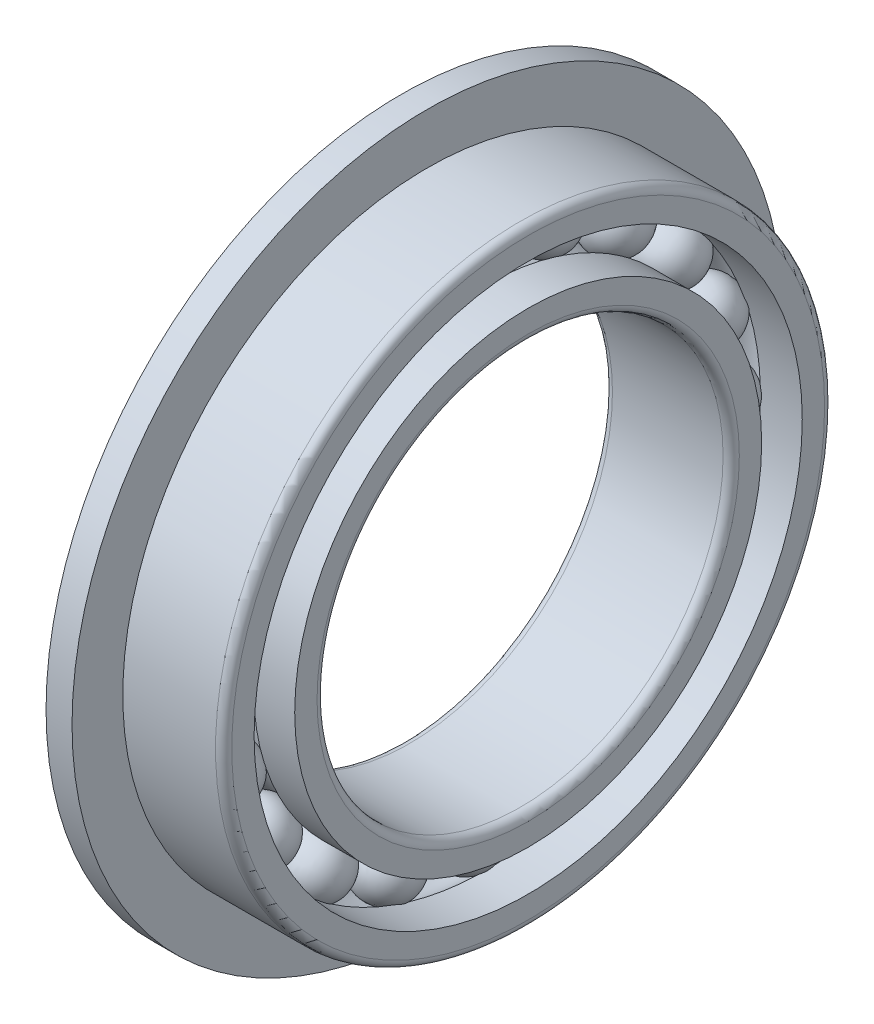
SolidWorks part; units mm, degrees
material "AISI 316 Stainless Steel Sheet (SS)"
ref_plane "Plane1" through (0, 0, 0) normal (0, 0, 1) x (1, 0, 0)
ref_plane "Plane2" through (0, 0, 0) normal (0, 1, 0) x (1, 0, 0)
ref_plane "Plane3" through (0, 0, 0) normal (1, 0, 0) x (0, 0, -1)
sketch "Clipboard" plane through (0, 0, 0) normal (0, 0, 1) x (1, 0, 0)
  line L0 (-10, 0) -> (10, 0) construction
  line L1 (0, 0) -> (21.0122, -7.6478)
  line L2 (0, 0) -> (7.4588, 2.7148)
  line L3 (0, 0) -> (21.0122, -7.6478)
  line L4 (0, 0) -> (-22.3573, -0.3902)
  dimension "BallCLRad" = 7.9375
sketch "CagSpiSke" plane through (0, 0, 0) normal (0, 0, 1) x (1, 0, 0)
  line L0 (0.0952, 7.7787) -> (0.0953, 8.0962)
  line L1 (0.0953, 8.0962) -> (-0.0953, 8.0962)
  line L2 (-0.0953, 8.0962) -> (-0.0952, 7.7787)
  line L3 (-0.0952, 7.7787) -> (0.0952, 7.7787)
  line L4 (-20.6375, 0) -> (20.6375, 0) construction
  line L5 (0, 0) -> (0, 23.7692) construction
  dimension "OD" = 16.1925
  dimension "ID" = 15.5575
revolve "CageSpine" add sketch "CagSpiSke" angle 0.001 about L4 reverse direction yes
ref_axis "Axis1" through (-50, 0, 0) along (1, 0, 0)
sketch "CagBalSke" plane through (0, 0, 0) normal (0, 0, 1) x (1, 0, 0)
  line L0 (-1.0478, 7.9375) -> (1.0478, 7.9375)
  line L1 (-1.905, 7.9375) -> (1.905, 7.9375) construction
  line L2 (-10, 0) -> (10, 0) construction
  line L3 (0, 0) -> (0, 24) construction
  arc A0 (1.0478, 7.9375) -> (-1.0478, 7.9375) centre (0, 7.9375) cw
  dimension "BallCLRad" = 7.9375
revolve "CageBall" [suppressed] add sketch "CagBalSke" angle 360 about L1 reverse direction yes
pattern_circular "CageBalls" [suppressed] count 20 every 18 about axis through (-50, 0, 0) along (1, 0, 0)
sketch "CagTrmODSke" plane through (0, 0, 0) normal (0, 0, 1) x (1, 0, 0)
  line L0 (1.0732, 8.0962) -> (1.0732, 9.0107)
  line L1 (1.0732, 9.0107) -> (-1.0732, 9.0107)
  line L2 (-1.0732, 9.0107) -> (-1.0732, 8.0962)
  line L3 (-1.0732, 8.0962) -> (1.0732, 8.0962)
  line L4 (-20.6375, 0) -> (20.6375, 0) construction
  line L5 (0, 0) -> (0, 25) construction
  dimension "Width" = 2.1463
  dimension "ID" = 16.1925
  dimension "OD" = 18.0213
revolve "CageTrimOD" [suppressed] cut sketch "CagTrmODSke" angle 360 about L4 reverse direction yes
sketch "CagTrmIDSke" plane through (0, 0, 0) normal (0, 0, 1) x (1, 0, 0)
  line L0 (1.0732, 6.9151) -> (1.0732, 7.7787)
  line L1 (1.0732, 7.7787) -> (-1.0732, 7.7787)
  line L2 (-1.0732, 7.7787) -> (-1.0732, 6.9151)
  line L3 (-1.0732, 6.9151) -> (1.0732, 6.9151)
  line L4 (-20.6375, 0) -> (20.6375, 0) construction
  line L5 (0, 0) -> (0, 25) construction
  dimension "Width" = 2.1463
  dimension "ID" = 13.8303
  dimension "OD" = 15.5575
revolve "CageTrimID" [suppressed] cut sketch "CagTrmIDSke" angle 360 about L4 reverse direction yes
sketch "BalSimSke" plane through (0, 0, 0) normal (0, 0, 1) x (1, 0, 0)
  line L0 (-10, 0) -> (10, 0) construction
  line L1 (-10, 7.9375) -> (10, 7.9375) construction
  line L2 (0, 0) -> (0, 23) construction
  circle A0 centre (0, 7.9375) radius 0.9525
  dimension "BallCLRad" = 7.9375
  dimension "Ball_diameter" = 1.905
revolve "BallsSimplified" [suppressed] add sketch "BalSimSke" angle 360 about L0
sketch "BalDetSke" plane through (0, 0, 0) normal (0, 0, 1) x (1, 0, 0)
  line L0 (-0.9525, 7.9375) -> (0.9525, 7.9375)
  line L1 (-1.905, 7.9375) -> (1.905, 7.9375) construction
  line L2 (0, 0) -> (0, 25) construction
  arc A0 (0.9525, 7.9375) -> (-0.9525, 7.9375) centre (0, 7.9375) cw
  dimension "BallCLRad" = 7.9375
  dimension "Ball_diameter" = 1.905
revolve "BallDetailed" add sketch "BalDetSke" angle 360 about L1 reverse direction yes
sketch "InnRacSke" plane through (0, 0, 0) normal (0, 0, 1) x (1, 0, 0)
  line L0 (-0.6501, 7.3025) -> (-1.9837, 7.3025)
  line L1 (-1.9837, 7.3025) -> (-1.9837, 6.604)
  line L2 (-1.7297, 6.35) -> (1.7297, 6.35)
  line L3 (1.9837, 6.604) -> (1.9837, 7.3025)
  line L4 (1.9837, 7.3025) -> (0.7009, 7.3025)
  line L5 (-20.6375, 0) -> (20.6375, 0) construction
  line L6 (0, 0) -> (0, 30) construction
  arc A0 (-1.9837, 6.604) -> (-1.7297, 6.35) centre (-1.7297, 6.604) ccw
  arc A1 (1.7297, 6.35) -> (1.9837, 6.604) centre (1.7297, 6.604) ccw
  arc A2 (0.7009, 7.3025) -> (-0.6501, 7.3025) centre (0.0254, 7.9375) cw
  dimension "BallCLRad" = 7.9375
  dimension "Fillet_radius" = 0.254
  dimension "Ball_diameter" = 1.8542
  dimension "ID" = 12.7
  dimension "OD" = 14.605
  dimension "Width" = 3.9675
revolve "InnerRace" add sketch "InnRacSke" angle 360 about L5 reverse direction yes
sketch "OutRacSke" plane through (0, 0, 0) normal (0, 0, 1) x (1, 0, 0)
  line L0 (-0.6755, 8.5725) -> (-1.9837, 8.5725)
  line L1 (-1.9837, 8.5725) -> (-1.9837, 9.271)
  line L2 (-1.7297, 9.525) -> (1.7297, 9.525)
  line L3 (1.9837, 9.271) -> (1.9837, 8.5725)
  line L4 (1.9837, 8.5725) -> (0.6755, 8.5725)
  line L5 (-20.6375, 0) -> (20.6375, 0) construction
  line L6 (0, 0) -> (0, 30) construction
  arc A0 (-1.9837, 9.271) -> (-1.7297, 9.525) centre (-1.7297, 9.271) cw
  arc A1 (1.7297, 9.525) -> (1.9837, 9.271) centre (1.7297, 9.271) cw
  arc A2 (0.6755, 8.5725) -> (-0.6755, 8.5725) centre (0, 7.9375) ccw
  dimension "BallCLRad" = 7.9375
  dimension "Fillet_radius" = 0.254
  dimension "Ball_diameter" = 1.8542
  dimension "Width" = 3.9675
revolve "OuterRace" add sketch "OutRacSke" angle 360 about L5 reverse direction yes
pattern_circular "BallsDetailed" count 20 every 18 about axis through (-50, 0, 0) along (1, 0, 0) of "BallDetailed"
sketch "Sketch1" plane through (0, 0, 0) normal (0, 0, 1) x (1, 0, 0)
  line L0 (0, 0) -> (-7.5958, 0) construction
  line L2 (-1.9837, 9.271) -> (-1.1709, 9.271)
  line L3 (-1.9837, 9.271) -> (-1.9837, 11.1125)
  line L4 (-1.9837, 11.1125) -> (-1.1709, 11.1125)
  line L5 (-1.1709, 9.271) -> (-1.1709, 11.1125)
  dimension "D1" = 11.1125
  dimension "D2" = 0.8128
revolve "Revolve1" add sketch "Sketch1" angle 360 about L0
equation "\"BallCLRad@Clipboard\" = ( \"OD@OutRacSke\" + \"ID@InnRacSke\" ) / 4"
equation "\"BallCLRad@BalSimSke\" = \"BallCLRad@Clipboard\""
equation "\"BallCLRad@BalDetSke\" = \"BallCLRad@Clipboard\""
equation "\"BallCLRad@InnRacSke\" = \"BallCLRad@Clipboard\""
equation "\"BallCLRad@OutRacSke\" = \"BallCLRad@Clipboard\""
equation "\"Ball_diameter@InnRacSke\" = \"Ball_diameter@BalDetSke\" - 0.002"
equation "\"Ball_diameter@OutRacSke\" = \"Ball_diameter@BalDetSke\" - 0.002"
equation "\"Ball_diameter@BalSimSke\" = \"Ball_diameter@BalDetSke\""
equation "\"Width@OutRacSke\" = \"Width@InnRacSke\""
equation "\"Fillet_radius@OutRacSke\" = \"Fillet_radius@InnRacSke\""
equation "\"Max_count@Clipboard\" = int( 3.14159265 / atn(( \"Ball_diameter@BalDetSke\" / 2) / sqr( \"BallCLRad@Clipboard\"  *  \"BallCLRad@Clipboard\" - ( \"Ball_diameter@BalDetSke\" / 2) *  ( \"Ball_diameter@BalDetSke\" / 2))))"
equation "\"Max_count@Clipboard\" = ((sgn( \"Max_count@Clipboard\" - \"Count@Clipboard\" )-1)*( \"Max_count@Clipboard\" - \"Count@Clipboard\" ))/-2+ \"Count@Clipboard\""
equation "\"Count@BallsDetailed\" = int( \"Show_count@Clipboard\" ) "
equation "\"Count@BallsDetailed\" = ((sgn( \"Count@BallsDetailed\" - \"Max_count@Clipboard\" )-1)*( \"Count@BallsDetailed\" - \"Max_count@Clipboard\" ))/-2+ \"Max_count@Clipboard\""
equation "\"Count@BallsDetailed\" = ((sgn( \"Count@BallsDetailed\" - \"Min_count@Clipboard\" )+1)*( \"Count@BallsDetailed\" - \"Min_count@Clipboard\"))/2 +\"Min_count@Clipboard\""
equation "\"Angle@BallsDetailed\" = 360.0 / \"Max_count@Clipboard\""
equation "\"BallCLRad@CagBalSke\" = \"BallCLRad@Clipboard\""
equation "\"Count@CageBalls\" = \"Count@BallsDetailed\""
equation "\"Angle@CageBalls\" = \"Angle@BallsDetailed\""
equation "\"Angle@CageSpine\" =  \"Angle@CageBalls\" * ( \"Count@CageBalls\" -1 + int( \"Count@CageBalls\" / \"Max_count@Clipboard\" ) )  + 0.001 -  int( \"Count@CageBalls\" / \"Max_count@Clipboard\" ) * 0.001"
equation "\"Angle@CageSpine\" =  \"Angle@CageSpine\" * int( \"Min_count@Clipboard\" / 2) + int(1 / \"Min_count@Clipboard\")  * 0.001"
equation "\"CageWallOD@CagBalSke\" =  \"Ball_diameter@BalDetSke\" * 1.1"
equation "\"Thickness@CagSpiSke\" =  \"Ball_diameter@BalDetSke\" * 0.1"
equation "\"OD@CagTrmODSke\" = \"BallCLRad@Clipboard\" * 2 + \"CageWallOD@CagBalSke\" + 0.002"
equation "\"ID@CagTrmODSke\" = \"BallCLRad@Clipboard\" * 2 + \"Ball_diameter@BalDetSke\" / 6"
equation "\"OD@CagTrmIDSke\" = \"BallCLRad@Clipboard\" * 2 - \"Ball_diameter@BalDetSke\" / 6"
equation "\"ID@CagTrmIDSke\" = \"BallCLRad@Clipboard\" * 2 - \"CageWallOD@CagBalSke\" + 0.002"
equation "\"OD@CagSpiSke\" = \"ID@CagTrmODSke\""
equation "\"ID@CagSpiSke\" = \"OD@CagTrmIDSke\""
equation "\"Width@CagTrmODSke\" = \"CageWallOD@CagBalSke\" + 0.002"
equation "\"Width@CagTrmIDSke\" = \"CageWallOD@CagBalSke\" + 0.002"
